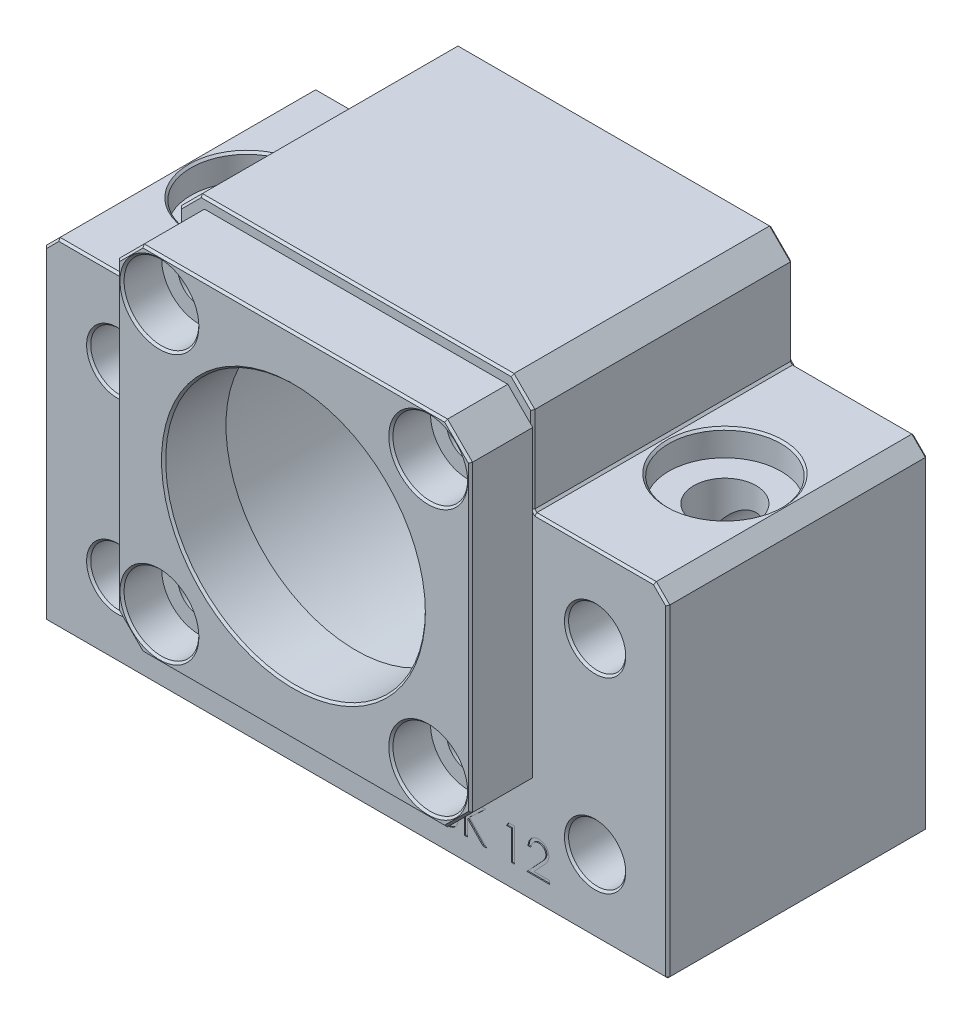
SolidWorks part; units mm, degrees
ref_plane "Front" through (0, 0, 0) normal (0, 0, 1) x (1, 0, 0)
ref_plane "Top" through (0, 0, 0) normal (0, 1, 0) x (1, 0, 0)
ref_plane "Right" through (0, 0, 0) normal (1, 0, 0) x (0, 0, -1)
sketch "Sketch2" plane through (0, 0, 0) normal (0, 0, 1) x (1, 0, 0)
  line L0 (30, -25) -> (-30, -25)
  line L1 (-30, -25) -> (-30, 7.5)
  line L2 (-30, 7.5) -> (-17, 7.5)
  line L3 (-17, 7.5) -> (-17, 18)
  line L4 (-17, 18) -> (17, 18)
  line L5 (0, 18) -> (0, -25) construction
  line L6 (17, 7.5) -> (17, 18)
  line L7 (30, 7.5) -> (17, 7.5)
  line L8 (30, -25) -> (30, 7.5)
  circle A0 centre (0, 0) radius 12.5
  circle A1 centre (-23, 0) radius 2.75
  circle A2 centre (23, 0) radius 2.75
  circle A3 centre (-23, -18) radius 2.75
  circle A4 centre (23, -18) radius 2.75
  circle A5 centre (23, 0) radius 2.75
  dimension "D3" = 25
  dimension "D9" = 5.5
  dimension "D1" = 60
  dimension "D2" = 32.5
  dimension "D4" = 34
  dimension "D5" = 43
  dimension "D6" = 2
  dimension "D7" = 46
  dimension "D8" = 18
extrude "Boss-Extrude1" add sketch "Sketch2" against normal blind 25 contours L5 L4 L3 L2 L1 L0 A1 A3 | L4 L5 L0 L8 L7 L6 A4 A2 region at (15.9751, -6.7721, 0) region at (-15.9751, -6.7721, 0)
chamfer "Chamfer1" distance 2 angle 45 2 edges at (17, 18, -12.5) (-17, 18, -12.5)
sketch "Sketch7" plane through (0, 7.5, 0) normal (0, 1, 0) x (1, 0, 0)
  line L0 (0, 25) -> (0, 0) construction
  line L1 (-15, 25) -> (15, 25) construction
  line L2 (-30, 12.5) -> (-17, 12.5) construction
  line L3 (-30, 25) -> (-30, 0) construction
  line L4 (-17, 25) -> (-17, 0) construction
  circle A0 centre (-23, 12.5) radius 3
  circle A1 centre (23, 12.5) radius 3
  dimension "D1" = 6
  dimension "D2" = 46
extrude "Cut-Extrude4" cut sketch "Sketch7" against normal through all
sketch "Sketch8" plane through (0, 7.5, 0) normal (0, 1, 0) x (1, 0, 0)
  line L0 (0, 25) -> (0, 0) construction
  line L1 (-15, 25) -> (15, 25) construction
  line L2 (-15, 0) -> (15, 0) construction
  circle A0 centre (-23, 12.5) radius 5.4
  circle A1 centre (23, 12.5) radius 5.4
  dimension "D1" = 10.8
extrude "Cut-Extrude5" cut sketch "Sketch8" against normal blind 2.5
chamfer "Chamfer4" distance 0.2 angle 45 38 edges at (-23, -25, -9.5) (23, -25, -15.5) (25.75, 0, -25) (25.75, -18, -25) (-20.25, -18, -25) (-20.25, 0, -25) (25.75, 0, 0) (25.75, -18, 0) (-20.25, -18, 0) (-20.25, 0, 0) (30, -25, -12.5) (-30, -25, -12.5) (-16, 17, -25) (-17, 11.75, -25) (-23.5, 7.5, -25) (-30, -8.75, -25) (0, -25, -25) (30, -8.75, -25) (23.5, 7.5, -25) (0, 18, -25) (16, 17, -25) (17, 11.75, -25) (23.5, 7.5, 0) (30, -8.75, 0) (0, -25, 0) (-30, -8.75, 0) (-23.5, 7.5, 0) (-17, 7.5, -12.5) (-17, 11.75, 0) (-16, 17, 0) (0, 18, 0) (16, 17, 0) (17, 11.75, 0) (17, 7.5, -12.5) (23, 7.5, -17.9) (-23, 7.5, -7.1) (12.5, 0, -25) (12.5, 0, 0)
chamfer "Chamfer5" distance 1.3 angle 45 2 edges at (30, 7.5, -12.5) (-30, 7.5, -12.5)
chamfer "Chamfer6" distance 0.2 angle 45 4 edges at (29.35, 6.85, -25) (-29.35, 6.85, -25) (-29.35, 6.85, 0) (29.35, 6.85, 0)
ref_plane "Plane1" through (0, 0, 0) normal (0, 0, 1) x (1, 0, 0)
sketch "Sketch15" plane through (0, 0, 0) normal (0, 0, 1) x (1, 0, 0)
  line L0 (0, 17) -> (0, -27.027) construction
  line L1 (32.7156, 0) -> (-32.7881, 0) construction
  line L3 (17, -17) -> (-17, -17)
  line L4 (17, -17) -> (17, 17)
  line L5 (17, 17) -> (-17, 17)
  line L6 (-17, -17) -> (-17, 17)
  line L7 (17, -17) -> (-17, 17) construction
  line L8 (17, 17) -> (-17, -17) construction
  circle A0 centre (-0.0362, 0) radius 12.5
  point P5 (0, 0)
  dimension "D3" = 25
  dimension "D1" = 34
  dimension "D2" = 34
extrude "Boss-Extrude9" add sketch "Sketch15" along normal blind 6 separate body
ref_plane "Plane2" through (0, 0, 6) normal (0, 0, 1) x (1, 0, 0)
sketch "Sketch20" plane through (0, 0, 6) normal (0, 0, 1) x (1, 0, 0)
  line L0 (-17, 17) -> (17, -17) construction
  line L1 (17, 17) -> (-17, -17) construction
  line L2 (-17, 0) -> (17, 0) construction
  line L3 (-17, 17) -> (-17, -17) construction
  line L4 (17, -17) -> (17, 17) construction
  line L5 (0, 17) -> (0, -17) construction
  line L6 (17, 17) -> (-17, 17) construction
  line L7 (-17, -17) -> (17, -17) construction
  point P20 (-12.9401, 12.9401)
  point P21 (12.9401, 12.9401)
  point P22 (12.9401, -12.9401)
  point P23 (-12.9401, -12.9401)
  dimension "D1" = 18.3
chamfer "Chamfer8" distance 2.4 angle 45 4 edges at (17, -17, 3) (-17, -17, 3) (-17, 17, 3) (17, 17, 3)
hole_wizard "CBORE for M4 Hexagon socket head cap screws1" positions "3DSketch5" profile "Sketch22" counterbore size "M4" standard "GB"
sketch3d "3DSketch5"
  point P0 (12.9401, 12.9401, 6)
  point P3 (-12.9401, 12.9401, 6)
  point P6 (-12.9401, -12.9401, 6)
  point P9 (12.9401, -12.9401, 6)
sketch "Sketch22" plane through (12.9401, 12.9401, 6) normal (1, 0, 0) x (0, -1, 0)
  line L0 (0, 0) -> (0, 21.2318)
  line L1 (0, 21.2318) -> (2.05, 20)
  line L2 (2.05, 20) -> (2.05, 3.82)
  line L3 (2.05, 3.82) -> (3.6, 3.82)
  line L4 (3.6, 3.82) -> (3.6, 0)
  line L5 (3.6, 0) -> (0, 0)
  line L10 (0, 21.2318) -> (-2.05, 20) construction
  line L11 (0, -6.35) -> (0, 107.95) construction
  dimension "Hole Dia." = 4.1
  dimension "Hole Depth" = 20
  dimension "C'Bore Dia." = 7.2
  dimension "C'Bore Depth" = 3.82
  dimension "Drill Angle" = 118
chamfer "Chamfer11" distance 0.2 angle 45 13 edges at (-15.8, -15.8, 6) (-17, 0, 6) (-15.8, 15.8, 6) (0, 17, 6) (15.8, 15.8, 6) (17, 0, 6) (15.8, -15.8, 6) (0, -17, 6) (16.5401, -12.9401, 6) (-9.3401, -12.9401, 6) (-9.3401, 12.9401, 6) (16.5401, 12.9401, 6) (12.4638, 0, 6)
sketch "Sketch25" plane through (0, 0, 0) normal (0, 0, 1) x (1, 0, 0)
  circle A0 centre (0, 0) radius 16
  dimension "D1" = 32
extrude "Cut-Extrude8" cut sketch "Sketch25" against normal blind 20
sketch "Sketch28" plane through (0, 0, 0) normal (0, 0, 1) x (1, 0, 0)
  text T0 "BK 12" font "Century Gothic" height in points 12
extrude "Cut-Extrude9" cut sketch "Sketch28" against normal blind 0.1
